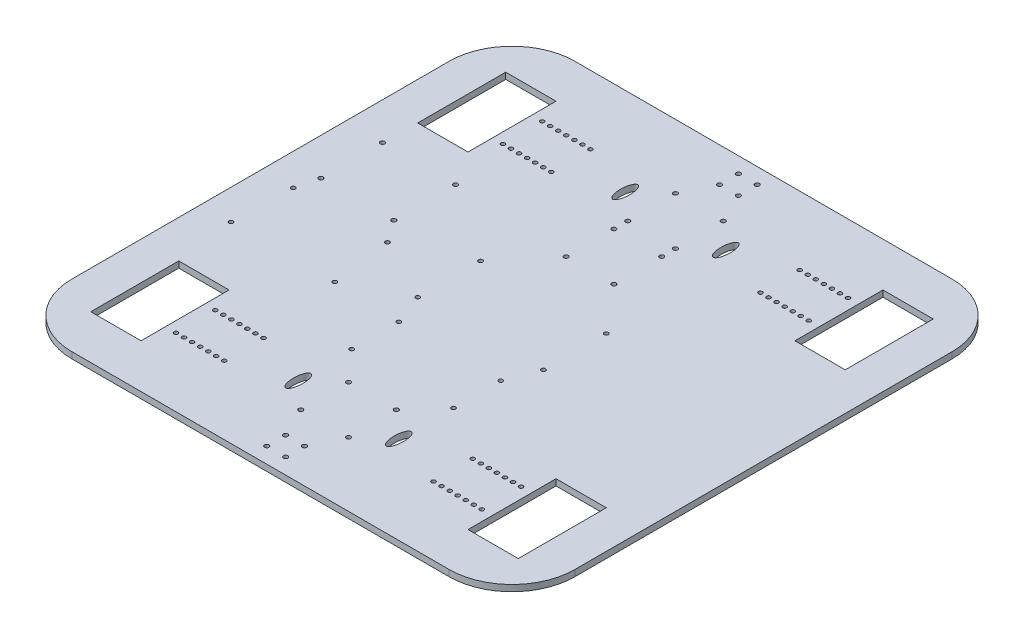
SolidWorks part; units mm, degrees
ref_plane "Front Plane" through (0, 0, 0) normal (0, 0, 1) x (1, 0, 0)
ref_plane "Top Plane" through (0, 0, 0) normal (0, 1, 0) x (1, 0, 0)
ref_plane "Right Plane" through (0, 0, 0) normal (1, 0, 0) x (0, 0, -1)
sketch "Sketch1" plane through (0, 0, 0) normal (0, 1, 0) x (1, 0, 0)
  line L0 (0, -1000) -> (0, 49000) construction
  line L1 (-170, 165) -> (-130, 165)
  line L2 (-170, 165) -> (-170, 95)
  line L3 (-170, 95) -> (-130, 95)
  line L4 (-130, 165) -> (-130, 95)
  line L5 (170, 95) -> (130, 95)
  line L6 (130, 165) -> (130, 95)
  line L7 (170, 165) -> (130, 165)
  line L8 (170, 165) -> (170, 95)
  line L9 (-1000, 0) -> (49000, 0) construction
  line L10 (-10, 190) -> (10, 190)
  line L11 (-10, 190) -> (-10, 170)
  line L12 (-10, 170) -> (10, 170)
  line L13 (10, 190) -> (10, 170)
  line L14 (-1010, 180) -> (48990, 180) construction
  line L15 (-1010, -180) -> (48990, -180) construction
  line L16 (0, 1000) -> (0, -49000) construction
  line L17 (-10, -170) -> (10, -170)
  line L18 (10, -190) -> (10, -170)
  line L19 (-10, -190) -> (10, -190)
  line L20 (-10, -190) -> (-10, -170)
  line L21 (170, -165) -> (170, -95)
  line L22 (-200, 200) -> (200, 200)
  line L23 (-200, 200) -> (-200, -200)
  line L24 (-200, -200) -> (200, -200)
  line L25 (200, 200) -> (200, -200)
  line L26 (170, -165) -> (130, -165)
  line L27 (130, -165) -> (130, -95)
  line L28 (170, -95) -> (130, -95)
  line L29 (-170, -95) -> (-130, -95)
  line L30 (-130, -165) -> (-130, -95)
  line L31 (-170, -165) -> (-130, -165)
  line L32 (-170, -165) -> (-170, -95)
  circle A0 centre (0, 0) radius 200 construction
  circle A1 centre (-7.5, 187.5) radius 1.75
  circle A2 centre (7.5, 187.5) radius 1.75
  circle A3 centre (7.5, 172.5) radius 1.75
  circle A4 centre (-7.5, 172.5) radius 1.75
  circle A5 centre (7.5, -187.5) radius 1.75
  circle A6 centre (-7.5, -187.5) radius 1.75
  circle A7 centre (-7.5, -172.5) radius 1.75
  circle A8 centre (7.5, -172.5) radius 1.75
  point P8 (-150, 165)
  point P19 (0, 190)
  point P22 (-10, 180)
  dimension "D1" = 400
  dimension "D7" = 3.5
  dimension "D2" = 40
  dimension "D3" = 70
  dimension "D4" = 150
  dimension "D5" = 20
  dimension "D6" = 180
  dimension "D8" = 2.5
  dimension "D9" = 2.5
  dimension "D10" = 35
extrude "Boss-Extrude2" add sketch "Sketch1" along normal blind 5 contours L25 L22 L23 L24 L1 L4 L3 L2 L7 L8 L5 L6 L10 L13 L12 L11 L19 L20 L17 L18 | L20 L19 L18 L17 A6 A5 A7 A8 | L13 L10 L11 L12 A2 A1 A3 A4 region at (0, 0, -180) region at (0, 0, 180) region at (0, 0, 0)
fillet "Fillet1" radius 50 4 edges at (200, 2.5, -200) (200, 2.5, 200) (-200, 2.5, 200) (-200, 2.5, -200)
sketch "Sketch2" plane through (0, 5, 0) normal (0, 1, 0) x (1, 0, 0)
  line L0 (-1094.0419, 130) -> (48905.9581, 130) construction
  line L1 (-130, 148.8) -> (-78.5, 148.8) construction
  line L2 (-130, 148.8) -> (-130, 111.2) construction
  line L3 (-130, 111.2) -> (-78.5, 111.2) construction
  line L4 (-78.5, 148.8) -> (-78.5, 111.2) construction
  line L5 (-130, 165) -> (-130, 95) construction
  line L6 (-170, 165) -> (-170, 95) construction
  line L7 (0, -1000) -> (0, 49000) construction
  line L8 (130, 111.2) -> (78.5, 111.2) construction
  line L9 (78.5, 148.8) -> (78.5, 111.2) construction
  line L10 (130, 148.8) -> (78.5, 148.8) construction
  line L11 (130, 148.8) -> (130, 111.2) construction
  line L12 (-1000, 0) -> (49000, 0) construction
  line L13 (130, -148.8) -> (130, -111.2) construction
  line L14 (130, -148.8) -> (78.5, -148.8) construction
  line L15 (78.5, -148.8) -> (78.5, -111.2) construction
  line L16 (130, -111.2) -> (78.5, -111.2) construction
  line L17 (-78.5, -148.8) -> (-78.5, -111.2) construction
  line L18 (-130, -111.2) -> (-78.5, -111.2) construction
  line L19 (-130, -148.8) -> (-130, -111.2) construction
  line L20 (-130, -148.8) -> (-78.5, -148.8) construction
  line L21 (-1094.0419, -130) -> (48905.9581, -130) construction
  circle A0 centre (-121.6, 145.6) radius 1.6
  circle A1 centre (-115.2, 145.6) radius 1.6
  circle A2 centre (-108.8, 145.6) radius 1.6
  circle A3 centre (-102.4, 145.6) radius 1.6
  circle A4 centre (-96, 145.6) radius 1.6
  circle A5 centre (-89.6, 145.6) radius 1.6
  circle A6 centre (-83.2, 145.6) radius 1.6
  circle A7 centre (-83.2, 114.4) radius 1.6
  circle A8 centre (-89.6, 114.4) radius 1.6
  circle A9 centre (-96, 114.4) radius 1.6
  circle A10 centre (-102.4, 114.4) radius 1.6
  circle A11 centre (-108.8, 114.4) radius 1.6
  circle A12 centre (-115.2, 114.4) radius 1.6
  circle A13 centre (-121.6, 114.4) radius 1.6
  circle A14 centre (83.2, 114.4) radius 1.6
  circle A15 centre (89.6, 114.4) radius 1.6
  circle A16 centre (96, 114.4) radius 1.6
  circle A17 centre (102.4, 114.4) radius 1.6
  circle A18 centre (108.8, 114.4) radius 1.6
  circle A19 centre (115.2, 114.4) radius 1.6
  circle A20 centre (121.6, 114.4) radius 1.6
  circle A21 centre (83.2, 145.6) radius 1.6
  circle A22 centre (89.6, 145.6) radius 1.6
  circle A23 centre (96, 145.6) radius 1.6
  circle A24 centre (102.4, 145.6) radius 1.6
  circle A25 centre (108.8, 145.6) radius 1.6
  circle A26 centre (115.2, 145.6) radius 1.6
  circle A27 centre (121.6, 145.6) radius 1.6
  circle A28 centre (121.6, -145.6) radius 1.6
  circle A29 centre (115.2, -145.6) radius 1.6
  circle A30 centre (108.8, -145.6) radius 1.6
  circle A31 centre (102.4, -145.6) radius 1.6
  circle A32 centre (96, -145.6) radius 1.6
  circle A33 centre (89.6, -145.6) radius 1.6
  circle A34 centre (83.2, -145.6) radius 1.6
  circle A35 centre (121.6, -114.4) radius 1.6
  circle A36 centre (115.2, -114.4) radius 1.6
  circle A37 centre (108.8, -114.4) radius 1.6
  circle A38 centre (102.4, -114.4) radius 1.6
  circle A39 centre (96, -114.4) radius 1.6
  circle A40 centre (89.6, -114.4) radius 1.6
  circle A41 centre (83.2, -114.4) radius 1.6
  circle A42 centre (-121.6, -114.4) radius 1.6
  circle A43 centre (-115.2, -114.4) radius 1.6
  circle A44 centre (-108.8, -114.4) radius 1.6
  circle A45 centre (-102.4, -114.4) radius 1.6
  circle A46 centre (-96, -114.4) radius 1.6
  circle A47 centre (-89.6, -114.4) radius 1.6
  circle A48 centre (-83.2, -114.4) radius 1.6
  circle A49 centre (-83.2, -145.6) radius 1.6
  circle A50 centre (-89.6, -145.6) radius 1.6
  circle A51 centre (-96, -145.6) radius 1.6
  circle A52 centre (-102.4, -145.6) radius 1.6
  circle A53 centre (-108.8, -145.6) radius 1.6
  circle A54 centre (-115.2, -145.6) radius 1.6
  circle A55 centre (-121.6, -145.6) radius 1.6
  point P9 (-130, 130)
  point P40 (-170, 130)
  dimension "D3" = 3.2
  dimension "D7" = 6.4
  dimension "D5" = 8.4
  dimension "D1" = 37.6
  dimension "D2" = 4.7
  dimension "D4" = 31.2
  dimension "D6" = 7
extrude "Cut-Extrude1" cut sketch "Sketch2" against normal blind 5
sketch "Sketch3" plane through (0, 5, 0) normal (0, 1, 0) x (1, 0, 0)
  line L0 (-150, -200) -> (150, -200) construction
  line L1 (-190, 3.34) -> (-88.4, 3.34) construction
  line L2 (-190, 3.34) -> (-190, -50) construction
  line L3 (-190, -50) -> (-88.4, -50) construction
  line L4 (-88.4, 3.34) -> (-88.4, -50) construction
  line L5 (-200, 150) -> (-200, -150) construction
  circle A0 centre (-176.03, -47.46) radius 1.65
  circle A1 centre (-174.76, 0.8) radius 1.65
  circle A2 centre (-93.48, -47.46) radius 1.65
  circle A3 centre (-99.83, 0.8) radius 1.65
  dimension "D5" = 3.3
  dimension "D8" = 3.3
  dimension "D9" = 96.52
  dimension "D10" = 90.17
  dimension "D1" = 101.6
  dimension "D2" = 53.34
  dimension "D3" = 13.97
  dimension "D4" = 2.54
  dimension "D6" = 15.24
  dimension "D7" = 50.8
  dimension "D11" = 150
  dimension "D12" = 10
extrude "Cut-Extrude2" cut sketch "Sketch3" against normal blind 10 contours A1 | A2 | L2 L1 L4 L3 | A0 | A3 region at (-174.76, 5, -0.8) region at (-93.48, 5, 47.46)
sketch "Sketch4" plane through (0, 5, 0) normal (0, 1, 0) x (1, 0, 0)
  line L0 (-19, 149) -> (19, 149) construction
  line L1 (-1149.7342, 130) -> (48850.2658, 130) construction
  line L2 (-22, 152) -> (22, 152) construction
  line L3 (-22, 152) -> (-22, 108) construction
  line L4 (-22, 108) -> (22, 108) construction
  line L5 (22, 152) -> (22, 108) construction
  line L6 (-19, 111) -> (19, 111) construction
  line L7 (-19, 100) -> (19, 100) construction
  line L8 (-1231.3219, 81) -> (48768.6781, 81) construction
  line L9 (-22, 103) -> (22, 103) construction
  line L10 (-22, 103) -> (-22, 59) construction
  line L11 (-22, 59) -> (22, 59) construction
  line L12 (22, 103) -> (22, 59) construction
  line L13 (-19, 62) -> (19, 62) construction
  line L14 (-19, -149) -> (19, -149) construction
  line L15 (-22, -152) -> (22, -152) construction
  line L16 (-130, 165) -> (-130, 95) construction
  line L17 (-150, 200) -> (150, 200) construction
  line L18 (22, -108) -> (22, -152) construction
  line L19 (-22, -108) -> (-22, -152) construction
  line L20 (-19, -111) -> (19, -111) construction
  line L21 (-22, -108) -> (22, -108) construction
  line L22 (-1022, -130) -> (48978, -130) construction
  line L23 (-130, -165) -> (-130, -95) construction
  circle A0 centre (-19, 149) radius 1.75
  circle A1 centre (19, 149) radius 1.75
  circle A2 centre (19, 111) radius 1.75
  circle A3 centre (-19, 111) radius 1.75
  circle A4 centre (-19, 100) radius 1.75
  circle A5 centre (19, 100) radius 1.75
  circle A6 centre (19, 62) radius 1.75
  circle A7 centre (-19, 62) radius 1.75
  circle A8 centre (-19, -149) radius 1.75
  circle A9 centre (19, -149) radius 1.75
  circle A10 centre (-19, -111) radius 1.75
  circle A11 centre (19, -111) radius 1.75
  point P9 (0, 149)
  point P10 (0, 152)
  point P14 (-22, 130)
  point P26 (0, 100)
  point P27 (0, 103)
  point P31 (-22, 81)
  point P38 (-130, 130)
  point P39 (0, 200)
  point P40 (0, 108)
  point P56 (-22, -130)
  point P58 (-130, -130)
  dimension "D1" = 3.5
  dimension "D5" = 3.5
  dimension "D2" = 38
  dimension "D3" = 44
  dimension "D4" = 38
  dimension "D6" = 38
  dimension "D7" = 44
  dimension "D8" = 38
  dimension "D9" = 5
  dimension "D10" = 2
extrude "Cut-Extrude3" cut sketch "Sketch4" against normal blind 10
sketch "Sketch5" plane through (0, 5, 0) normal (0, 1, 0) x (1, 0, 0)
  line L0 (-1136.3236, 43) -> (48863.6764, 43) construction
  line L1 (-174, 15) -> (-89, 15) construction
  line L2 (-174, 15) -> (-174, 71) construction
  line L3 (-174, 71) -> (-89, 71) construction
  line L4 (-89, 15) -> (-89, 71) construction
  line L5 (-180, 10) -> (-83, 10) construction
  line L6 (-180, 10) -> (-180, 76) construction
  line L7 (-180, 76) -> (-83, 76) construction
  line L8 (-83, 10) -> (-83, 76) construction
  line L9 (-200, 150) -> (-200, -150) construction
  line L10 (-150, -200) -> (150, -200) construction
  circle A0 centre (-170.5, 67.5) radius 1.75
  circle A1 centre (-112.5, 67.5) radius 1.75
  circle A2 centre (-112.5, 18.5) radius 1.75
  circle A3 centre (-170.5, 18.5) radius 1.75
  dimension "D4" = 3.5
  dimension "D5" = 3.5
  dimension "D1" = 56
  dimension "D2" = 85
  dimension "D3" = 58
  dimension "D6" = 3.5
  dimension "D7" = 49
  dimension "D8" = 3.5
  dimension "D9" = 5
  dimension "D10" = 5
  dimension "D11" = 6
  dimension "D12" = 6
  dimension "D13" = 20
  dimension "D14" = 210
extrude "Cut-Extrude4" cut sketch "Sketch5" against normal blind 10
sketch "Sketch6" plane through (0, 5, 0) normal (0, 1, 0) x (1, 0, 0)
  line L0 (-130, 165) -> (-130, 95) construction
  line L1 (0, -800) -> (0, 49200) construction
  line L2 (-150, 200) -> (150, 200) construction
  line L3 (-1200, 0) -> (48800, 0) construction
  line L4 (-200, 150) -> (-200, -150) construction
  ellipse E0 centre (-40, 130) end of major axis (-40, 140) minor radius 3.75
  ellipse E1 centre (40, 130) end of major axis (40, 140) minor radius 3.75
  ellipse E2 centre (40, -130) end of major axis (40, -140) minor radius 3.75
  ellipse E3 centre (-40, -130) end of major axis (-40, -140) minor radius 3.75
  point P13 (-130, 130)
  point P14 (-200, 0)
  point P26 (0, 200)
  dimension "D1" = 90
  dimension "D2" = 20
  dimension "D3" = 7.5
extrude "Cut-Extrude5" cut sketch "Sketch6" against normal blind 10
sketch "Sketch7" plane through (0, 5, 0) normal (0, 1, 0) x (1, 0, 0)
  line L0 (0, -1008.1082) -> (0, 48991.8918) construction
  line L1 (-53, 28) -> (53, 28) construction
  line L2 (-53, 28) -> (-53, -28) construction
  line L3 (-53, -28) -> (53, -28) construction
  line L4 (53, 28) -> (53, -28) construction
  line L5 (-53, 28) -> (-47, 28) construction
  line L6 (-53, 28) -> (-53, 22) construction
  line L7 (-53, 22) -> (-47, 22) construction
  line L8 (-47, 28) -> (-47, 22) construction
  line L9 (-1053, 0) -> (48947, 0) construction
  line L10 (-150, -200) -> (150, -200) construction
  line L11 (-200, 150) -> (-200, -150) construction
  circle A1 centre (-50, 25) radius 1.65
  circle A2 centre (50, 25) radius 1.65
  circle A3 centre (50, -25) radius 1.65
  circle A4 centre (-50, -25) radius 1.65
  point P10 (-50, 22)
  point P15 (-47, 25)
  point P16 (0, 28)
  point P17 (-53, 0)
  point P25 (0, -200)
  point P28 (-200, 0)
  point P29 (-50, 25)
  dimension "D3" = 3.3
  dimension "D1" = 106
  dimension "D2" = 56
  dimension "D5" = 6
  dimension "D6" = 6
extrude "Cut-Extrude6" cut sketch "Sketch7" against normal blind 10
sketch "Sketch8" plane through (0, 5, 0) normal (0, 1, 0) x (1, 0, 0)
  line L0 (0, -1046.6714) -> (0, 48953.3286) construction
  line L1 (-43.5, -46.5) -> (43.5, -46.5) construction
  line L2 (-43.5, -46.5) -> (-43.5, -90) construction
  line L3 (-43.5, -90) -> (43.5, -90) construction
  line L4 (43.5, -46.5) -> (43.5, -90) construction
  line L5 (-43.5, -46.5) -> (-37.5, -46.5) construction
  line L6 (-43.5, -46.5) -> (-43.5, -52.5) construction
  line L7 (-43.5, -52.5) -> (-37.5, -52.5) construction
  line L8 (-37.5, -46.5) -> (-37.5, -52.5) construction
  line L9 (-1043.5, -68.25) -> (48956.5, -68.25) construction
  line L10 (37.5, -46.5) -> (37.5, -52.5) construction
  line L11 (43.5, -52.5) -> (37.5, -52.5) construction
  line L12 (-150, -200) -> (150, -200) construction
  circle A0 centre (-40.5, -49.5) radius 1.65
  circle A1 centre (40.5, -49.5) radius 1.65
  circle A2 centre (40.5, -87) radius 1.65
  circle A3 centre (-40.5, -87) radius 1.65
  point P10 (-40.5, -52.5)
  point P11 (-37.5, -49.5)
  point P15 (0, -46.5)
  point P17 (-43.5, -68.25)
  point P28 (0, -200)
  dimension "D3" = 3.3
  dimension "D1" = 87
  dimension "D2" = 6
  dimension "D4" = 43.5
  dimension "D5" = 110
extrude "Cut-Extrude7" cut sketch "Sketch8" against normal blind 5
